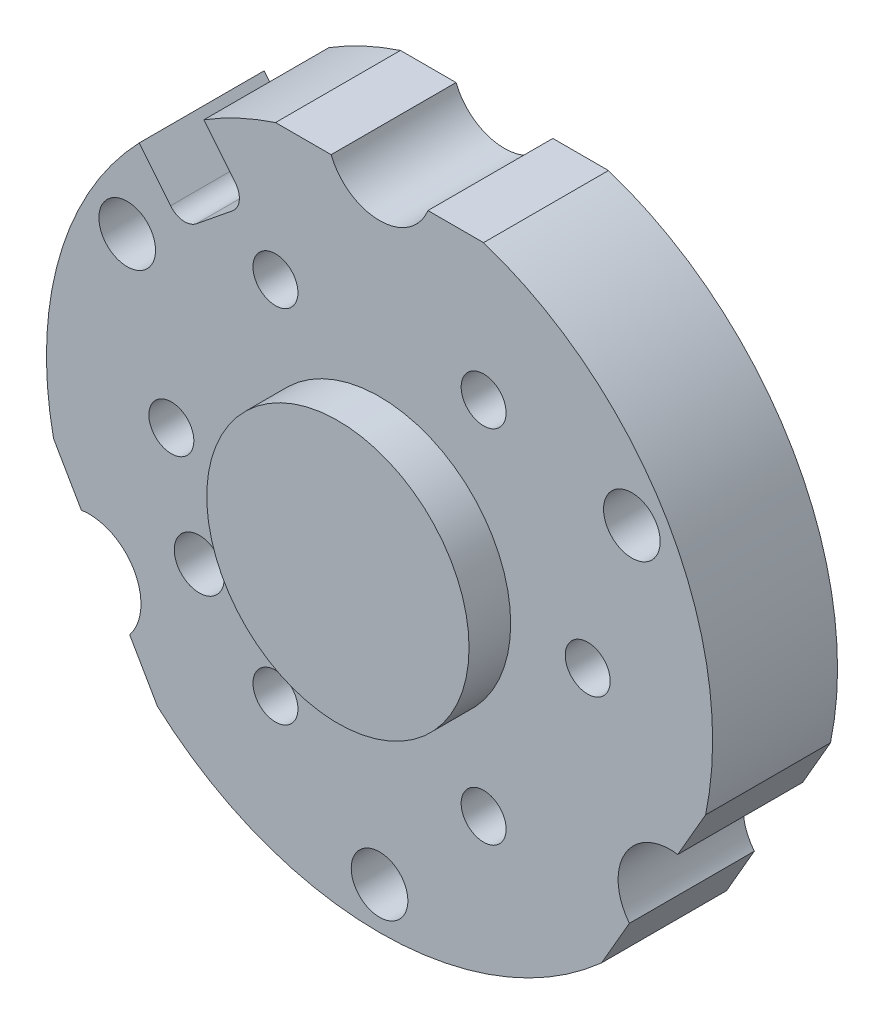
SolidWorks part; units mm, degrees
ref_plane "Piano frontale" through (0, 0, 0) normal (0, 0, 1) x (1, 0, 0)
ref_plane "Piano superiore" through (0, 0, 0) normal (0, 1, 0) x (1, 0, 0)
ref_plane "Piano destro" through (0, 0, 0) normal (1, 0, 0) x (0, 0, -1)
sketch "Schizzo1" plane through (0, 0, 0) normal (0, 0, 1) x (1, 0, 0)
  line L9 (-5.8114, 38) -> (-12.49, 38)
  line L10 (-21.0896, 33.9886) -> (-17.3224, 29.3364)
  line L11 (-17.6476, 26.2422) -> (-21.9996, 22.718)
  line L12 (-25.0938, 23.0432) -> (-28.8611, 27.6954)
  line L13 (-39.154, -8.1833) -> (-35.8146, -13.9673)
  line L14 (-30.0029, -24.0334) -> (-26.664, -29.8167)
  line L15 (26.664, -29.8167) -> (30.0029, -24.0334)
  line L16 (35.8146, -13.9673) -> (39.154, -8.1833)
  line L17 (12.49, 38) -> (5.8114, 38)
  line L18 (-5.8114, 38) -> (-12.49, 38)
  line L19 (-21.0896, 33.9886) -> (-17.3224, 29.3364)
  line L20 (-17.6476, 26.2422) -> (-21.9996, 22.718)
  line L21 (-25.0938, 23.0432) -> (-28.8611, 27.6954)
  line L22 (-39.154, -8.1833) -> (-35.8146, -13.9673)
  line L23 (-30.0029, -24.0334) -> (-26.664, -29.8167)
  line L24 (26.664, -29.8167) -> (30.0029, -24.0334)
  line L25 (35.8146, -13.9673) -> (39.154, -8.1833)
  line L26 (12.49, 38) -> (5.8114, 38)
  arc A9 (-12.49, 38) -> (-21.0896, 33.9886) centre (0, 0) ccw
  arc A10 (-17.6476, 26.2422) -> (-17.3224, 29.3364) centre (-19.0321, 27.9519) ccw
  arc A11 (-25.0938, 23.0432) -> (-21.9996, 22.718) centre (-23.3841, 24.4277) ccw
  arc A12 (-28.8611, 27.6954) -> (-39.154, -8.1833) centre (0, 0) ccw
  arc A13 (-30.0029, -24.0334) -> (-35.8146, -13.9673) centre (-34.9, -20.15) ccw
  arc A14 (-26.664, -29.8167) -> (26.664, -29.8167) centre (0, 0) ccw
  arc A15 (35.8146, -13.9673) -> (30.0029, -24.0334) centre (34.9, -20.15) ccw
  arc A16 (39.154, -8.1833) -> (12.49, 38) centre (0, 0) ccw
  arc A17 (-5.8114, 38) -> (5.8114, 38) centre (0, 40.3) ccw
  arc A18 (-12.49, 38) -> (-21.0896, 33.9886) centre (0, 0) ccw
  arc A19 (-17.6476, 26.2422) -> (-17.3224, 29.3364) centre (-19.0321, 27.9519) ccw
  arc A20 (-25.0938, 23.0432) -> (-21.9996, 22.718) centre (-23.3841, 24.4277) ccw
  arc A21 (-28.8611, 27.6954) -> (-39.154, -8.1833) centre (0, 0) ccw
  arc A22 (-30.0029, -24.0334) -> (-35.8146, -13.9673) centre (-34.9, -20.15) ccw
  arc A23 (-26.664, -29.8167) -> (26.664, -29.8167) centre (0, 0) ccw
  arc A24 (35.8146, -13.9673) -> (30.0029, -24.0334) centre (34.9, -20.15) ccw
  arc A25 (39.154, -8.1833) -> (12.49, 38) centre (0, 0) ccw
  arc A26 (-5.8114, 38) -> (5.8114, 38) centre (0, 40.3) ccw
  dimension "D1" = 0
extrude "Estrusione-Estrusione1" add sketch "Schizzo1" along normal up to surface (15 mm away)
sketch "Schizzo5" plane through (0, 0, 0) normal (0, 0, -1) x (-1, 0, 0)
  arc A0 (0, -27.5) -> (0, 27.5) centre (0, 0) ccw construction
  arc A1 (0, 27.5) -> (0, -27.5) centre (0, 0) ccw construction
  arc A2 (0, -27.5) -> (0, 27.5) centre (0, 0) ccw
  arc A3 (0, 27.5) -> (0, -27.5) centre (0, 0) ccw
extrude "Estrusione-Estrusione5" add sketch "Schizzo5" along normal blind 0.3 contours A3 A2
sketch "Schizzo2" plane through (0, 0, 15) normal (0, 0, 1) x (1, 0, 0)
  arc A0 (26.25, -2.1651) -> (23.75, 2.1651) centre (25, 0) ccw construction
  arc A1 (23.75, 2.1651) -> (26.25, -2.1651) centre (25, 0) ccw construction
  arc A2 (11.25, 23.8157) -> (13.75, 19.4856) centre (12.5, 21.6506) ccw construction
  arc A3 (13.75, 19.4856) -> (11.25, 23.8157) centre (12.5, 21.6506) ccw construction
  arc A4 (-23.75, -2.1651) -> (-26.25, 2.1651) centre (-25, 0) ccw construction
  arc A5 (-26.25, 2.1651) -> (-23.75, -2.1651) centre (-25, 0) ccw construction
  arc A6 (-23.1506, -9.9019) -> (-20.1506, -15.0981) centre (-21.6506, -12.5) ccw construction
  arc A7 (-20.1506, -15.0981) -> (-23.1506, -9.9019) centre (-21.6506, -12.5) ccw construction
  arc A8 (-13.75, 23.8157) -> (-11.25, 19.4856) centre (-12.5, 21.6506) ccw construction
  arc A9 (-11.25, 19.4856) -> (-13.75, 23.8157) centre (-12.5, 21.6506) ccw construction
  arc A10 (11.25, -19.4856) -> (13.75, -23.8157) centre (12.5, -21.6506) ccw construction
  arc A11 (-13.75, -19.4856) -> (-11.25, -23.8157) centre (-12.5, -21.6506) ccw construction
  arc A12 (-11.25, -23.8157) -> (-13.75, -19.4856) centre (-12.5, -21.6506) ccw construction
  arc A13 (13.75, -23.8157) -> (11.25, -19.4856) centre (12.5, -21.6506) ccw construction
  arc A14 (26.25, -2.1651) -> (23.75, 2.1651) centre (25, 0) ccw
  arc A15 (23.75, 2.1651) -> (26.25, -2.1651) centre (25, 0) ccw
  arc A16 (11.25, 23.8157) -> (13.75, 19.4856) centre (12.5, 21.6506) ccw
  arc A17 (13.75, 19.4856) -> (11.25, 23.8157) centre (12.5, 21.6506) ccw
  arc A18 (-23.75, -2.1651) -> (-26.25, 2.1651) centre (-25, 0) ccw
  arc A19 (-26.25, 2.1651) -> (-23.75, -2.1651) centre (-25, 0) ccw
  arc A20 (-23.1506, -9.9019) -> (-20.1506, -15.0981) centre (-21.6506, -12.5) ccw
  arc A21 (-20.1506, -15.0981) -> (-23.1506, -9.9019) centre (-21.6506, -12.5) ccw
  arc A22 (-13.75, 23.8157) -> (-11.25, 19.4856) centre (-12.5, 21.6506) ccw
  arc A23 (-11.25, 19.4856) -> (-13.75, 23.8157) centre (-12.5, 21.6506) ccw
  arc A24 (11.25, -19.4856) -> (13.75, -23.8157) centre (12.5, -21.6506) ccw
  arc A25 (-13.75, -19.4856) -> (-11.25, -23.8157) centre (-12.5, -21.6506) ccw
  arc A26 (-11.25, -23.8157) -> (-13.75, -19.4856) centre (-12.5, -21.6506) ccw
  arc A27 (13.75, -23.8157) -> (11.25, -19.4856) centre (12.5, -21.6506) ccw
  arc A28 (-11.15, 19.3124) -> (-13.85, 23.9889) centre (-12.5, 21.6506) ccw
  arc A29 (-13.85, 23.9889) -> (-11.15, 19.3124) centre (-12.5, 21.6506) ccw
  arc A30 (11.15, 23.9889) -> (13.85, 19.3124) centre (12.5, 21.6506) ccw
  arc A31 (13.85, 19.3124) -> (11.15, 23.9889) centre (12.5, 21.6506) ccw
  arc A32 (26.35, -2.3383) -> (23.65, 2.3383) centre (25, 0) ccw
  arc A33 (23.65, 2.3383) -> (26.35, -2.3383) centre (25, 0) ccw
  arc A34 (13.85, -23.9889) -> (11.15, -19.3124) centre (12.5, -21.6506) ccw
  arc A35 (11.15, -19.3124) -> (13.85, -23.9889) centre (12.5, -21.6506) ccw
  arc A36 (-11.15, -23.9889) -> (-13.85, -19.3124) centre (-12.5, -21.6506) ccw
  arc A37 (-13.85, -19.3124) -> (-11.15, -23.9889) centre (-12.5, -21.6506) ccw
  arc A38 (-23.65, -2.3383) -> (-26.35, 2.3383) centre (-25, 0) ccw
  arc A39 (-26.35, 2.3383) -> (-23.65, -2.3383) centre (-25, 0) ccw
  dimension "D1" = 0.2
extrude "Taglio-Estrusione1" cut sketch "Schizzo2" against normal through all contours A31 A30 | A29 A28 | A38 A39 | A21 A20 | A36 A37 | A34 A35 | A32 A33
sketch "Schizzo3" plane through (0, 0, 0) normal (0, 0, -1) x (-1, 0, 0)
  arc A0 (30.3, 20.9) -> (30.3, 14.1) centre (30.3, 17.5) ccw construction
  arc A1 (30.3, 14.1) -> (30.3, 20.9) centre (30.3, 17.5) ccw construction
  arc A2 (0, -38.4) -> (0, -31.6) centre (0, -35) ccw construction
  arc A3 (0, -31.6) -> (0, -38.4) centre (0, -35) ccw construction
  arc A4 (-30.3, 20.9) -> (-30.3, 14.1) centre (-30.3, 17.5) ccw construction
  arc A5 (-30.3, 14.1) -> (-30.3, 20.9) centre (-30.3, 17.5) ccw construction
  arc A6 (30.3, 20.9) -> (30.3, 14.1) centre (30.3, 17.5) ccw
  arc A7 (30.3, 14.1) -> (30.3, 20.9) centre (30.3, 17.5) ccw
  arc A8 (0, -38.4) -> (0, -31.6) centre (0, -35) ccw
  arc A9 (0, -31.6) -> (0, -38.4) centre (0, -35) ccw
  arc A10 (-30.3, 20.9) -> (-30.3, 14.1) centre (-30.3, 17.5) ccw
  arc A11 (-30.3, 14.1) -> (-30.3, 20.9) centre (-30.3, 17.5) ccw
extrude "Taglio-Estrusione2" cut sketch "Schizzo3" against normal through all
sketch "Schizzo4" plane through (0, 0, 15) normal (0, 0, 1) x (1, 0, 0)
  arc A0 (-7.875, 13.6399) -> (7.875, -13.6399) centre (0, 0) ccw construction
  arc A1 (7.875, -13.6399) -> (-7.875, 13.6399) centre (0, 0) ccw construction
  arc A2 (-7.875, 13.6399) -> (7.875, -13.6399) centre (0, 0) ccw
  arc A3 (7.875, -13.6399) -> (-7.875, 13.6399) centre (0, 0) ccw
extrude "Estrusione-Estrusione2" add sketch "Schizzo4" along normal blind 5
sketch "Schizzo7" plane through (0, 0, -0.3) normal (0, 0, -1) x (-1, 0, 0)
  circle A0 centre (-12.5, 21.6506) radius 6
  circle A1 centre (12.5, 21.6506) radius 6
  circle A2 centre (25, 0) radius 6
  circle A4 centre (12.5, -21.6506) radius 6
  circle A5 centre (-12.5, -21.6506) radius 6
  circle A6 centre (-25, 0) radius 6
  dimension "D1" = 12
extrude "Taglio-Estrusione3" cut sketch "Schizzo7" against normal blind 7
